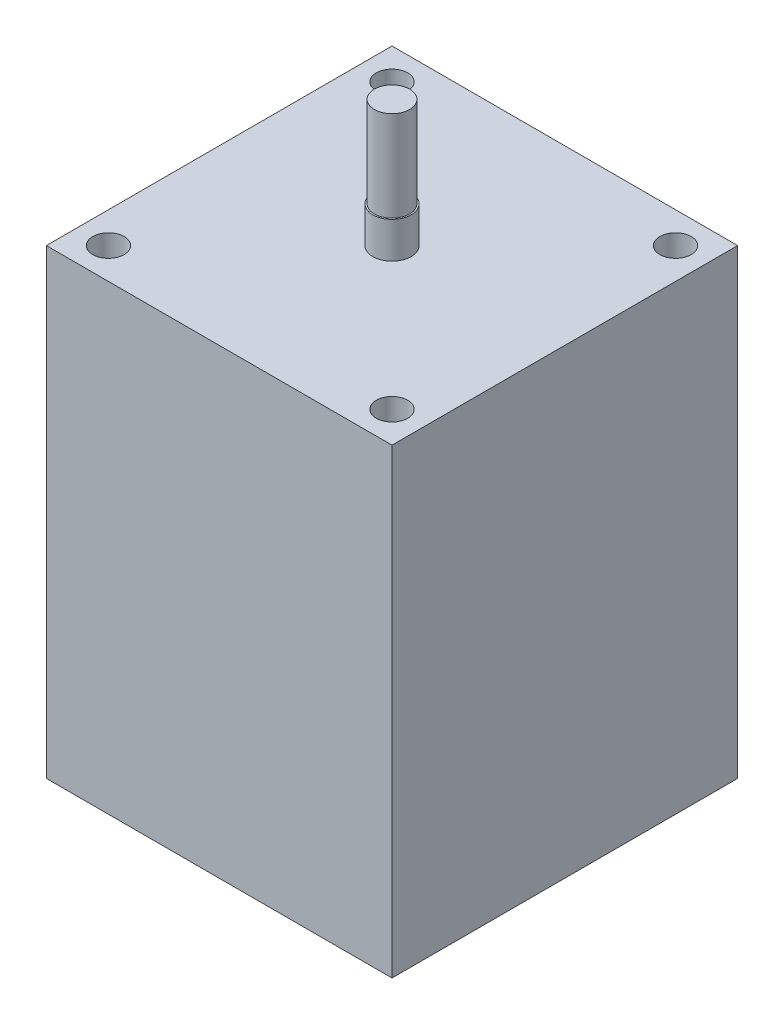
SolidWorks part; units mm, degrees
ref_plane "Front Plane" through (0, 0, 0) normal (0, 0, 1) x (1, 0, 0)
ref_plane "Top Plane" through (0, 0, 0) normal (0, 1, 0) x (1, 0, 0)
ref_plane "Right Plane" through (0, 0, 0) normal (1, 0, 0) x (0, 0, -1)
sketch "Sketch1" plane through (0, 0, 0) normal (0, 1, 0) x (1, 0, 0)
  line L1 (0, 0) -> (57.3, 0)
  line L2 (0, 0) -> (0, -57.3)
  line L3 (0, -57.3) -> (57.3, -57.3)
  line L4 (57.3, 0) -> (57.3, -57.3)
  circle A0 centre (5.15, -5.15) radius 2.6
  circle A1 centre (52.15, -5.15) radius 2.6
  circle A2 centre (5.15, -52.15) radius 2.6
  circle A3 centre (52.15, -52.15) radius 2.6
  circle A4 centre (28.65, -28.65) radius 3.175
  circle A5 centre (28.65, -28.65) radius 2.925
  dimension "D5" = 5.2
  dimension "D6" = 6.35
  dimension "D7" = 5.85
  dimension "D1" = 57.3
  dimension "D2" = 57.3
  dimension "D3" = 47
  dimension "D4" = 47
  dimension "D8" = 28.65
  dimension "D9" = 28.65
  dimension "D10" = 5.15
  dimension "D11" = 5.15
extrude "Boss-Extrude1" add sketch "Sketch1" along normal blind 76.5 contours L4 L1 L2 L3 A4 A3 A2 A1 A0 region at (28.65, 0, 0.8103)
extrude "Boss-Extrude2" add sketch "Sketch1<4>" along normal blind 82.5 contours A4 A5 region at (25.5648, 0, 28.65)
sketch "Sketch1<4>" plane through (0, 0, 0) normal (0, 1, 0) x (1, 0, 0) same geometry as "Sketch1"
extrude "Boss-Extrude3" add sketch "Sketch1<5>" along normal blind 97.5 contours A5 region at (28.65, 0, 28.65)
sketch "Sketch1<5>" plane through (0, 0, 0) normal (0, 1, 0) x (1, 0, 0) same geometry as "Sketch1"
equation "\"D8@Sketch1\"=\"D1@Sketch1\"/2"
equation "\"D9@Sketch1\"=\"D2@Sketch1\"/2"
equation "\"D10@Sketch1\"=(\"D1@Sketch1\"-\"D3@Sketch1\")/2"
equation "\"D11@Sketch1\"=(\"D1@Sketch1\"-\"D3@Sketch1\")/2"
